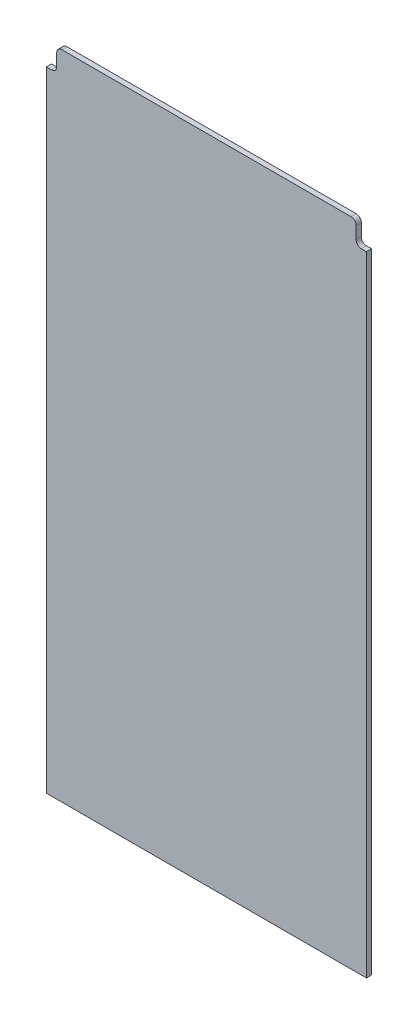
SolidWorks part; units mm, degrees
material "Acrylic (Medium-high impact)"
ref_plane "Front Plane" through (0, 0, 0) normal (0, 0, 1) x (1, 0, 0)
ref_plane "Top Plane" through (0, 0, 0) normal (0, 1, 0) x (1, 0, 0)
ref_plane "Right Plane" through (0, 0, 0) normal (1, 0, 0) x (0, 0, -1)
sketch "Sketch1" plane through (0, 0, 0) normal (0, 0, 1) x (1, 0, 0)
  line L0 (83.6105, -361.95) -> (83.6105, 175.26) construction
  line L1 (281.197, -361.95) -> (83.6105, -361.95)
  line L2 (281.197, -361.95) -> (281.197, 40.3225)
  line L3 (281.197, 40.3225) -> (83.6105, 40.3225)
  line L4 (83.6105, -361.95) -> (83.6105, 40.3225)
  line L5 (281.197, -361.95) -> (83.6105, 40.3225) construction
  line L6 (281.197, 40.3225) -> (83.6105, -361.95) construction
  line L7 (97.0763, 41.91) -> (153.4312, 41.91) construction
  point P4 (182.4037, -160.8138)
  dimension "D1" = 1.5875
extrude "Boss-Extrude1" add sketch "Sketch1" along normal blind 3.175
sketch "Sketch3" plane through (0, 0, 3.175) normal (0, 0, 1) x (1, 0, 0)
  line L0 (281.197, 40.3225) -> (83.6105, 40.3225) construction
  line L1 (89.9605, 40.3225) -> (83.6105, 40.3225)
  line L2 (89.9605, 40.3225) -> (89.9605, 26.3525)
  line L3 (89.9605, 26.3525) -> (83.6105, 26.3525)
  line L4 (83.6105, 40.3225) -> (83.6105, 26.3525)
  line L5 (89.9605, 40.3225) -> (83.6105, 26.3525) construction
  line L6 (89.9605, 26.3525) -> (83.6105, 40.3225) construction
  line L7 (83.6105, 40.3225) -> (83.6105, -361.95) construction
  line L8 (182.4037, 40.3225) -> (182.4037, -361.95) construction
  line L9 (83.6105, -361.95) -> (281.197, -361.95) construction
  line L10 (274.847, 26.3525) -> (281.197, 40.3225) construction
  line L11 (274.847, 40.3225) -> (281.197, 26.3525) construction
  line L12 (281.197, 40.3225) -> (281.197, 26.3525)
  line L13 (274.847, 26.3525) -> (281.197, 26.3525)
  line L14 (274.847, 40.3225) -> (274.847, 26.3525)
  line L15 (274.847, 40.3225) -> (281.197, 40.3225)
  point P4 (86.7855, 33.3375)
  point P17 (278.022, 33.3375)
  dimension "D1" = 13.97
  dimension "D2" = 6.35
extrude "Cut-Extrude1" cut sketch "Sketch3" against normal through all
fillet "Fillet1" radius 3.175 4 edges at (89.9605, 26.3525, 1.5875) (89.9605, 40.3225, 1.5875) (274.847, 40.3225, 1.5875) (274.847, 26.3525, 1.5875)
